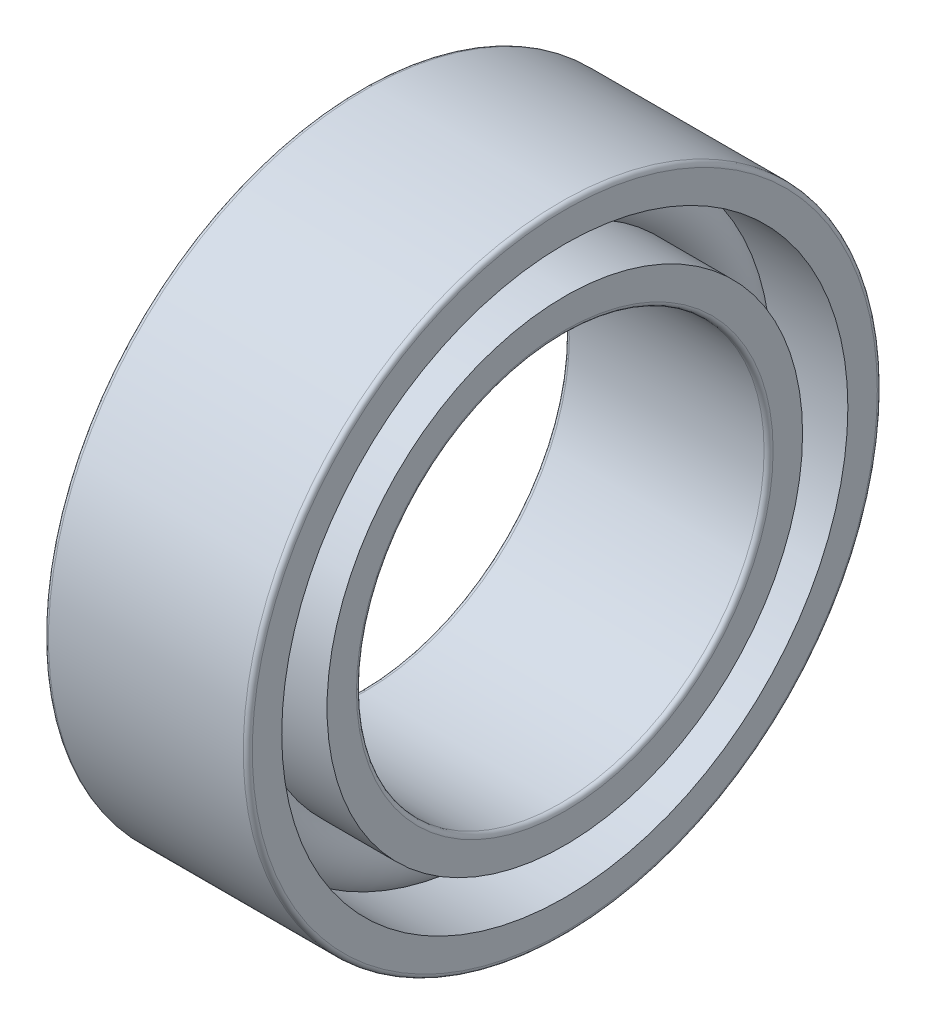
SolidWorks part; units mm, degrees
ref_plane "Plane1" through (0, 0, 0) normal (0, 0, 1) x (1, 0, 0)
ref_plane "Plane2" through (0, 0, 0) normal (0, 1, 0) x (1, 0, 0)
ref_plane "Plane3" through (0, 0, 0) normal (1, 0, 0) x (0, 0, -1)
sketch "Clipboard" plane through (0, 0, 0) normal (0, 0, 1) x (1, 0, 0)
  line L0 (-10, 0) -> (10, 0) construction
  line L1 (0, 0) -> (22.3471, -0.7804)
  line L2 (0, 0) -> (5.7465, 0.2007)
  line L3 (0, 0) -> (22.3471, -0.7804)
  line L4 (0, 0) -> (-22.3573, -0.3902)
  dimension "BallCLRad" = 5.75
sketch "CagSpiSke" plane through (0, 0, 0) normal (0, 0, 1) x (1, 0, 0)
  line L0 (0.075, 5.625) -> (0.075, 5.875)
  line L1 (0.075, 5.875) -> (-0.075, 5.875)
  line L2 (-0.075, 5.875) -> (-0.075, 5.625)
  line L3 (-0.075, 5.625) -> (0.075, 5.625)
  line L4 (-20.6375, 0) -> (20.6375, 0) construction
  line L5 (0, 0) -> (0, 23.7692) construction
  dimension "OD" = 11.75
  dimension "ID" = 11.25
revolve "CageSpine" add sketch "CagSpiSke" angle 0.001 about L4 reverse direction yes
ref_axis "Axis1" through (-50, 0, 0) along (1, 0, 0)
sketch "CagBalSke" plane through (0, 0, 0) normal (0, 0, 1) x (1, 0, 0)
  line L0 (-0.825, 5.75) -> (0.825, 5.75)
  line L1 (-1.905, 5.75) -> (1.905, 5.75) construction
  line L2 (-10, 0) -> (10, 0) construction
  line L3 (0, 0) -> (0, 24) construction
  arc A0 (0.825, 5.75) -> (-0.825, 5.75) centre (0, 5.75) cw
  dimension "BallCLRad" = 5.75
revolve "CageBall" [suppressed] add sketch "CagBalSke" angle 360 about L1 reverse direction yes
pattern_circular "CageBalls" [suppressed] count 2 every 180 about axis through (-50, 0, 0) along (1, 0, 0)
sketch "CagTrmODSke" plane through (0, 0, 0) normal (0, 0, 1) x (1, 0, 0)
  line L0 (0.826, 5.875) -> (0.826, 6.576)
  line L1 (0.826, 6.576) -> (-0.826, 6.576)
  line L2 (-0.826, 6.576) -> (-0.826, 5.875)
  line L3 (-0.826, 5.875) -> (0.826, 5.875)
  line L4 (-20.6375, 0) -> (20.6375, 0) construction
  line L5 (0, 0) -> (0, 25) construction
  dimension "Width" = 1.652
  dimension "ID" = 11.75
  dimension "OD" = 13.152
revolve "CageTrimOD" [suppressed] cut sketch "CagTrmODSke" angle 360 about L4 reverse direction yes
sketch "CagTrmIDSke" plane through (0, 0, 0) normal (0, 0, 1) x (1, 0, 0)
  line L0 (0.826, 4.926) -> (0.826, 5.625)
  line L1 (0.826, 5.625) -> (-0.826, 5.625)
  line L2 (-0.826, 5.625) -> (-0.826, 4.926)
  line L3 (-0.826, 4.926) -> (0.826, 4.926)
  line L4 (-20.6375, 0) -> (20.6375, 0) construction
  line L5 (0, 0) -> (0, 25) construction
  dimension "Width" = 1.652
  dimension "ID" = 9.852
  dimension "OD" = 11.25
revolve "CageTrimID" [suppressed] cut sketch "CagTrmIDSke" angle 360 about L4 reverse direction yes
sketch "BalSimSke" plane through (0, 0, 0) normal (0, 0, 1) x (1, 0, 0)
  line L0 (-10, 0) -> (10, 0) construction
  line L1 (-10, 5.75) -> (10, 5.75) construction
  line L2 (0, 0) -> (0, 23) construction
  circle A0 centre (0, 5.75) radius 0.75
  dimension "BallCLRad" = 5.75
  dimension "Ball_diameter" = 1.5
revolve "BallsSimplified" add sketch "BalSimSke" angle 360 about L0
sketch "BalDetSke" plane through (0, 0, 0) normal (0, 0, 1) x (1, 0, 0)
  line L0 (-0.75, 5.75) -> (0.75, 5.75)
  line L1 (-1.905, 5.75) -> (1.905, 5.75) construction
  line L2 (0, 0) -> (0, 25) construction
  arc A0 (0.75, 5.75) -> (-0.75, 5.75) centre (0, 5.75) cw
  dimension "BallCLRad" = 5.75
  dimension "Ball_diameter" = 1.5
revolve "BallDetailed" [suppressed] add sketch "BalDetSke" angle 360 about L1 reverse direction yes
sketch "InnRacSke" plane through (0, 0, 0) normal (0, 0, 1) x (1, 0, 0)
  line L0 (-0.525, 5.25) -> (-2.25, 5.25)
  line L1 (-2.25, 5.25) -> (-2.25, 4.6)
  line L2 (-2.15, 4.5) -> (2.15, 4.5)
  line L3 (2.25, 4.6) -> (2.25, 5.25)
  line L4 (2.25, 5.25) -> (0.525, 5.25)
  line L5 (-20.6375, 0) -> (20.6375, 0) construction
  line L6 (0, 0) -> (0, 30) construction
  arc A0 (-2.25, 4.6) -> (-2.15, 4.5) centre (-2.15, 4.6) ccw
  arc A1 (2.15, 4.5) -> (2.25, 4.6) centre (2.15, 4.6) ccw
  arc A2 (0.525, 5.25) -> (-0.525, 5.25) centre (0, 5.75) cw
  dimension "BallCLRad" = 5.75
  dimension "Fillet_radius" = 0.1
  dimension "Ball_diameter" = 1.45
  dimension "ID" = 9
  dimension "OD" = 10.5
  dimension "Width" = 4.5
revolve "InnerRace" add sketch "InnRacSke" angle 360 about L5 reverse direction yes
sketch "OutRacSke" plane through (0, 0, 0) normal (0, 0, 1) x (1, 0, 0)
  line L0 (-0.525, 6.25) -> (-2.25, 6.25)
  line L1 (-2.25, 6.25) -> (-2.25, 6.9)
  line L2 (-2.15, 7) -> (2.15, 7)
  line L3 (2.25, 6.9) -> (2.25, 6.25)
  line L4 (2.25, 6.25) -> (0.525, 6.25)
  line L5 (-20.6375, 0) -> (20.6375, 0) construction
  line L6 (0, 0) -> (0, 30) construction
  arc A0 (-2.25, 6.9) -> (-2.15, 7) centre (-2.15, 6.9) cw
  arc A1 (2.15, 7) -> (2.25, 6.9) centre (2.15, 6.9) cw
  arc A2 (0.525, 6.25) -> (-0.525, 6.25) centre (0, 5.75) ccw
  dimension "BallCLRad" = 5.75
  dimension "Fillet_radius" = 0.1
  dimension "Ball_diameter" = 1.45
  dimension "Width" = 4.5
revolve "OuterRace" add sketch "OutRacSke" angle 360 about L5 reverse direction yes
pattern_circular "BallsDetailed" [suppressed] count 2 every 180 about axis through (-50, 0, 0) along (1, 0, 0)
equation "\"BallCLRad@Clipboard\" = ( \"OD@OutRacSke\" + \"ID@InnRacSke\" ) / 4"
equation "\"BallCLRad@BalSimSke\" = \"BallCLRad@Clipboard\""
equation "\"BallCLRad@BalDetSke\" = \"BallCLRad@Clipboard\""
equation "\"BallCLRad@InnRacSke\" = \"BallCLRad@Clipboard\""
equation "\"BallCLRad@OutRacSke\" = \"BallCLRad@Clipboard\""
equation "\"Ball_diameter@InnRacSke\" = \"Ball_diameter@BalDetSke\" - 0.05"
equation "\"Ball_diameter@OutRacSke\" = \"Ball_diameter@BalDetSke\" - 0.05"
equation "\"Ball_diameter@BalSimSke\" = \"Ball_diameter@BalDetSke\""
equation "\"Width@OutRacSke\" = \"Width@InnRacSke\""
equation "\"Fillet_radius@OutRacSke\" = \"Fillet_radius@InnRacSke\""
equation "\"Max_count@Clipboard\" = int( 3.14159265 / atn(( \"Ball_diameter@BalDetSke\" / 2) / sqr( \"BallCLRad@Clipboard\"  *  \"BallCLRad@Clipboard\" - ( \"Ball_diameter@BalDetSke\" / 2) *  ( \"Ball_diameter@BalDetSke\" / 2))))"
equation "\"Max_count@Clipboard\" = ((sgn( \"Max_count@Clipboard\" - \"Count@Clipboard\" )-1)*( \"Max_count@Clipboard\" - \"Count@Clipboard\" ))/-2+ \"Count@Clipboard\""
equation "\"Count@BallsDetailed\" = int( \"Show_count@Clipboard\" ) "
equation "\"Count@BallsDetailed\" = ((sgn( \"Count@BallsDetailed\" - \"Max_count@Clipboard\" )-1)*( \"Count@BallsDetailed\" - \"Max_count@Clipboard\" ))/-2+ \"Max_count@Clipboard\""
equation "\"Count@BallsDetailed\" = ((sgn( \"Count@BallsDetailed\" - \"Min_count@Clipboard\" )+1)*( \"Count@BallsDetailed\" - \"Min_count@Clipboard\"))/2 +\"Min_count@Clipboard\""
equation "\"Angle@BallsDetailed\" = 360.0 / \"Max_count@Clipboard\""
equation "\"BallCLRad@CagBalSke\" = \"BallCLRad@Clipboard\""
equation "\"Count@CageBalls\" = \"Count@BallsDetailed\""
equation "\"Angle@CageBalls\" = \"Angle@BallsDetailed\""
equation "\"Angle@CageSpine\" =  \"Angle@CageBalls\" * ( \"Count@CageBalls\" -1 + int( \"Count@CageBalls\" / \"Max_count@Clipboard\" ) )  + 0.001 -  int( \"Count@CageBalls\" / \"Max_count@Clipboard\" ) * 0.001"
equation "\"Angle@CageSpine\" =  \"Angle@CageSpine\" * int( \"Min_count@Clipboard\" / 2) + int(1 / \"Min_count@Clipboard\")  * 0.001"
equation "\"CageWallOD@CagBalSke\" =  \"Ball_diameter@BalDetSke\" * 1.1"
equation "\"Thickness@CagSpiSke\" =  \"Ball_diameter@BalDetSke\" * 0.1"
equation "\"OD@CagTrmODSke\" = \"BallCLRad@Clipboard\" * 2 + \"CageWallOD@CagBalSke\" + 0.002"
equation "\"ID@CagTrmODSke\" = \"BallCLRad@Clipboard\" * 2 + \"Ball_diameter@BalDetSke\" / 6"
equation "\"OD@CagTrmIDSke\" = \"BallCLRad@Clipboard\" * 2 - \"Ball_diameter@BalDetSke\" / 6"
equation "\"ID@CagTrmIDSke\" = \"BallCLRad@Clipboard\" * 2 - \"CageWallOD@CagBalSke\" + 0.002"
equation "\"OD@CagSpiSke\" = \"ID@CagTrmODSke\""
equation "\"ID@CagSpiSke\" = \"OD@CagTrmIDSke\""
equation "\"Width@CagTrmODSke\" = \"CageWallOD@CagBalSke\" + 0.002"
equation "\"Width@CagTrmIDSke\" = \"CageWallOD@CagBalSke\" + 0.002"
